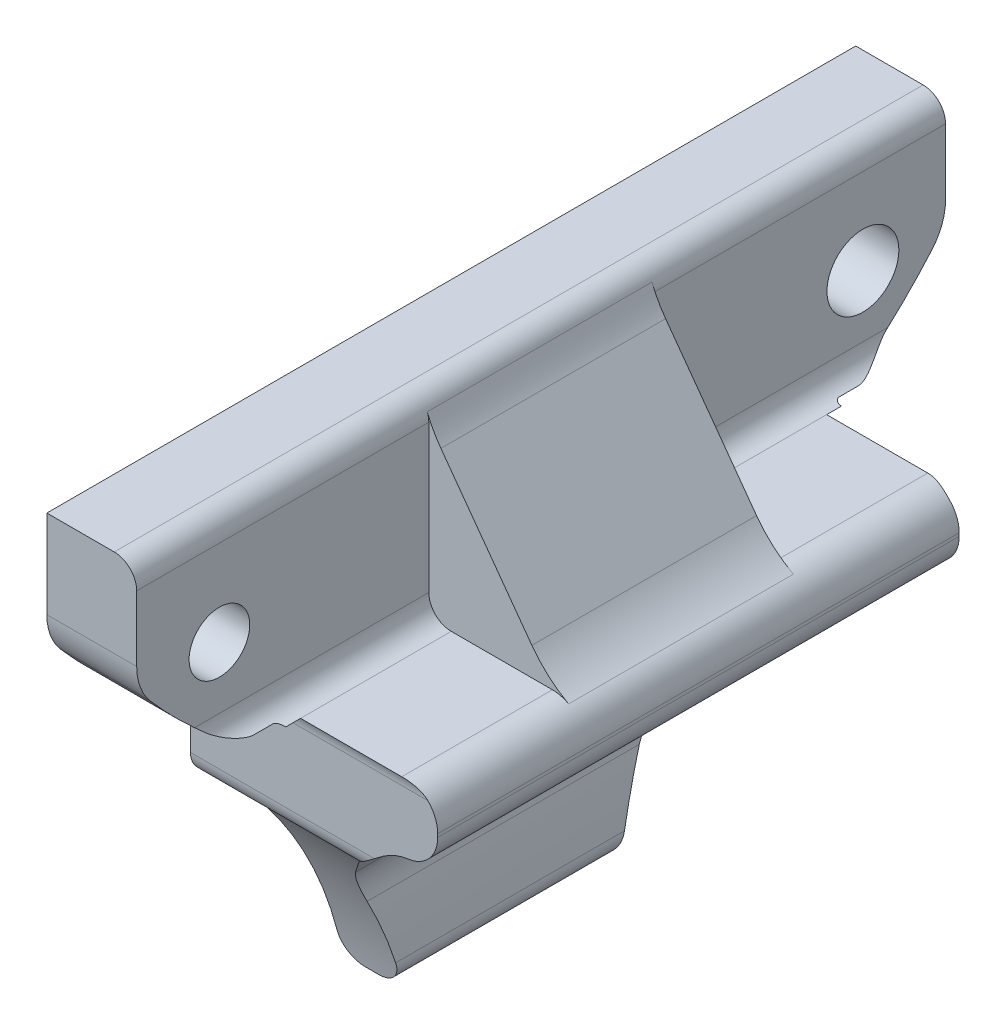
SolidWorks part; units mm, degrees
ref_plane "Front Plane" through (0, 0, 0) normal (0, 0, 1) x (1, 0, 0)
ref_plane "Top Plane" through (0, 0, 0) normal (0, 1, 0) x (1, 0, 0)
ref_plane "Right Plane" through (0, 0, 0) normal (1, 0, 0) x (0, 0, -1)
other "Configuration Table"
sketch "草图2" plane through (-34.0588, 0, 0) normal (1, 0, 0) x (0, 0, -1)
  line L0 (17.5003, 153.1924) -> (17.5003, 126.3596) construction
  line L1 (-17.4997, 126.3596) -> (-17.4997, 153.1924) construction
  line L2 (13.4167, 122.276) -> (8.6003, 122.276) construction
  line L3 (-4.8294, 122.276) -> (8.5706, 122.276) construction
  line L4 (-4.8997, 122.276) -> (-13.4161, 122.276) construction
  line L5 (17.5003, 130.276) -> (17.5003, 126.3596)
  line L6 (-17.4997, 126.3596) -> (-17.4997, 130.276)
  line L7 (13.4167, 122.276) -> (8.5706, 122.276)
  line L8 (-4.8294, 122.276) -> (8.5706, 122.276)
  line L9 (-4.8294, 122.276) -> (-13.4161, 122.276)
  line L10 (-17.4997, 130.276) -> (17.5003, 130.276)
  arc A0 (-17.4997, 126.3596) -> (-17.0119, 125.0507) centre (-15.4997, 126.3596) ccw construction
  arc A1 (17.0125, 125.0507) -> (17.5003, 126.3596) centre (15.5003, 126.3596) ccw construction
  arc A2 (14.7256, 122.7638) -> (17.0125, 125.0507) centre (0.0003, 139.776) ccw construction
  arc A3 (13.4167, 122.276) -> (14.7256, 122.7638) centre (13.4167, 124.276) ccw construction
  arc A4 (-17.0119, 125.0507) -> (-14.725, 122.7638) centre (0.0003, 139.776) ccw construction
  arc A5 (-14.725, 122.7638) -> (-13.4161, 122.276) centre (-13.4161, 124.276) ccw construction
  arc A6 (-17.4997, 126.3596) -> (-17.0119, 125.0507) centre (-15.4997, 126.3596) ccw
  arc A7 (17.0125, 125.0507) -> (17.5003, 126.3596) centre (15.5003, 126.3596) ccw
  arc A8 (14.7256, 122.7638) -> (17.0125, 125.0507) centre (0.0003, 139.776) ccw
  arc A9 (13.4167, 122.276) -> (14.7256, 122.7638) centre (13.4167, 124.276) ccw
  arc A10 (-17.0119, 125.0507) -> (-14.725, 122.7638) centre (0.0003, 139.776) ccw
  arc A11 (-14.725, 122.7638) -> (-13.4161, 122.276) centre (-13.4161, 124.276) ccw
  dimension "D1" = 8
extrude "凸台-拉伸1" add sketch "草图2" along normal blind 4
sketch "草图3" plane through (-30.0588, 0, 0) normal (1, 0, 0) x (0, 0, -1)
  line L0 (-13.4161, 122.276) -> (13.4167, 122.276) construction
  line L1 (-11.604, 122.276) -> (11.604, 122.276)
  line L2 (-11.604, 122.276) -> (-11.604, 106.7151)
  line L3 (-11.604, 106.7151) -> (11.604, 106.7151)
  line L4 (11.604, 122.276) -> (11.604, 106.7151)
  line L5 (0, 122.276) -> (0, 113.7703) construction
  point P6 (0, 122.276)
extrude "凸台-拉伸2" add sketch "草图3" against normal up to surface (67.5257 mm away)
sketch "草图7" plane through (0, 0, 11.604) normal (0, 0, 1) x (1, 0, 0)
  line L1 (-30.0588, 106.7151) -> (-23.0588, 106.7151)
  line L2 (-30.0588, 106.7151) -> (-30.0588, 121.7151)
  line L3 (-30.0588, 121.7151) -> (-23.0588, 121.7151)
  line L4 (-23.0588, 106.7151) -> (-23.0588, 121.7151)
  dimension "D1" = 7
  dimension "D2" = 15
extrude "凸台-拉伸3" add sketch "草图7" against normal up to surface (23.208 mm away) up to face at (-32.0588, 114.4955, -11.604)
sketch "草图11" plane through (0, 0, 11.604) normal (0, 0, 1) x (1, 0, 0)
  line L5 (-17.2607, 105.5707) -> (-17.8223, 118.1579)
  line L6 (-31.3247, 103.9771) -> (-17.2607, 105.5707)
  arc A11 (-25.4882, 118.1345) -> (-31.2955, 112.3272) centre (-10.0588, 96.8978) ccw
  arc A12 (-23.6542, 118.5853) -> (-25.4882, 118.1345) centre (-24.0187, 116.112) ccw
  arc A13 (-31.2955, 112.3272) -> (-31.7462, 110.4933) centre (-29.273, 110.8577) ccw
  arc A15 (-23.6542, 118.5853) -> (-17.8223, 118.1579) centre (-17.8223, 158.1579) ccw
  arc A17 (-31.3814, 106.8978) -> (-31.7462, 110.4933) centre (-71.3188, 104.6614) ccw
  arc A19 (-31.3247, 103.9771) -> (-31.3814, 106.8978) centre (-71.3188, 104.6614) ccw
extrude "切除-拉伸6" cut sketch "草图11" against normal blind 25
sketch "草图5" plane through (-30.0588, 0, 0) normal (1, 0, 0) x (0, 0, -1)
  arc A0 (-15.5686, 125.4571) -> (-13.0686, 125.4571) centre (-14.3186, 125.4571) ccw construction
  circle A1 centre (-14.3186, 125.4571) radius 1.25 construction
  arc A2 (15.5692, 125.4571) -> (13.0692, 125.4571) centre (14.3192, 125.4571) ccw construction
  circle A3 centre (14.3192, 125.4571) radius 1.25 construction
  circle A4 centre (-14.3186, 125.4571) radius 1.35
  circle A5 centre (14.3192, 125.4571) radius 1.6
  dimension "D1" = 2.7
  dimension "D2" = 3.2
extrude "切除-拉伸2" cut sketch "草图5" against normal blind 41
sketch "草图9" plane through (-30.0588, 0, 0) normal (1, 0, 0) x (0, 0, -1)
  circle A0 centre (-14.3186, 125.4571) radius 2.85
  circle A1 centre (14.3192, 125.4571) radius 2.85
  dimension "D1" = 5.7
  dimension "D2" = 5.7
extrude "切除-拉伸5" [suppressed] cut sketch "草图9" against normal blind 2
fillet "圆角7" [suppressed] radius 0.2
sketch "草图13" plane through (-34.0588, 0, 0) normal (-1, 0, 0) x (0, 0, 1)
  line L0 (-0.0003, 130.276) -> (0, 109.4709) construction
  line L1 (-17.5003, 130.276) -> (17.4997, 130.276) construction
  circle A0 centre (-15, 109.4709) radius 7.5
  circle A1 centre (15, 109.4714) radius 7.5
  dimension "D1" = 15
  dimension "D2" = 15
extrude "切除-拉伸7" [suppressed] cut sketch "草图13" against normal blind 14
fillet "圆角1" radius 1 2 edges at (-32.0588, 122.276, -11.604) (-32.0588, 122.276, 11.604)
sketch "草图16" plane through (-30.0588, 0, 0) normal (1, 0, 0) x (0, 0, -1)
  line L0 (22.0003, 103.276) -> (-14.3831, 103.276) construction
  line L1 (17.5003, 130.276) -> (-17.4997, 130.276) construction
  line L2 (0.0003, 130.276) -> (0.0003, 83.1608) construction
  circle A0 centre (22.0003, 103.276) radius 17.5
  circle A1 centre (-21.9997, 103.276) radius 17.5
  dimension "D2" = 35
  dimension "D1" = 27
  dimension "D3" = 22
extrude "切除-拉伸9" cut sketch "草图16" against normal through all both and the other way through all
sketch "草图17" plane through (-30.0588, 0, 0) normal (1, 0, 0) x (0, 0, -1)
  line L9 (-13.4161, 122.276) -> (-12.604, 122.276) construction
  line L14 (-17.4997, 130.276) -> (-17.4997, 126.3596) construction
  line L15 (-13.4161, 122.276) -> (-12.604, 122.276)
  line L16 (-17.4997, 130.276) -> (-17.4997, 126.3596)
  line L19 (-17.9997, 130.276) -> (-17.4997, 130.276)
  line L22 (-17.9997, 129.776) -> (-17.9997, 129.776)
  line L23 (-17.9997, 129.776) -> (-17.9997, 126.3596)
  line L24 (-13.4161, 121.776) -> (-12.604, 121.776)
  line L25 (-11.7055, 121.7151) -> (-12.3648, 121.7151)
  line L26 (-17.9997, 130.276) -> (-17.9997, 129.776)
  arc A4 (-11.7055, 121.7151) -> (-12.604, 122.276) centre (-12.604, 121.276) ccw construction
  arc A5 (-14.725, 122.7638) -> (-13.4161, 122.276) centre (-13.4161, 124.276) ccw construction
  arc A6 (-17.0119, 125.0507) -> (-14.725, 122.7638) centre (0.0003, 139.776) ccw construction
  arc A7 (-17.4997, 126.3596) -> (-17.0119, 125.0507) centre (-15.4997, 126.3596) ccw construction
  arc A9 (-11.7055, 121.7151) -> (-12.604, 122.276) centre (-12.604, 121.276) ccw
  arc A10 (-14.725, 122.7638) -> (-13.4161, 122.276) centre (-13.4161, 124.276) ccw
  arc A21 (-17.0119, 125.0507) -> (-14.725, 122.7638) centre (0.0003, 139.776) ccw
  arc A30 (-17.4997, 126.3596) -> (-17.0119, 125.0507) centre (-15.4997, 126.3596) ccw
  arc A36 (-17.9997, 126.3596) -> (-17.3899, 124.7235) centre (-15.4997, 126.3596) ccw
  arc A37 (-17.3899, 124.7235) -> (-15.0522, 122.3858) centre (0.0003, 139.776) ccw
  arc A38 (-15.0522, 122.3858) -> (-13.4161, 121.776) centre (-13.4161, 124.276) ccw
  arc A39 (-12.3648, 121.7151) -> (-12.604, 121.776) centre (-12.604, 121.276) ccw
  arc A41 (-12.1548, 121.4955) -> (-12.604, 121.776) centre (-12.604, 121.276) ccw construction
  arc A42 (-12.104, 121.276) -> (-12.1548, 121.4955) centre (-12.604, 121.276) ccw construction
  arc A43 (-11.604, 121.276) -> (-11.7055, 121.7151) centre (-12.604, 121.276) ccw construction
  dimension "D1" = 0.5
extrude "凸台-拉伸5" add sketch "草图17" against normal up to surface (4 mm away) up to face at (-34.0588, 127.0571, -14.3192)
ref_plane "基准面1" through (0, 0, 0) normal (0, 0, 1) x (1, 0, 0)
mirror "镜向1" about plane through (0, 0, 0) normal (0, 0, 1) of "凸台-拉伸5"
fillet "圆角8" radius 1 2 edges at (-30.2844, 117.3532, -11.604) (-30.2841, 117.3536, 11.604)
fillet "圆角10" radius 1 1 edges at (-30.0588, 130.276, 0)
fillet "圆角12" radius 1 2 edges at (-31.3716, 106.7151, -0.0003) (-34.0588, 106.7151, -0.0003)
fillet "圆角13" radius 1.5 2 edges at (-23.0588, 121.7151, 0) (-23.0588, 118.5021, 0)
ref_plane "基准面2" through (0, 0, 0) normal (0, 0, 1) x (1, 0, 0)
sketch "草图19" plane through (0, 0, 0) normal (0, 0, 1) x (1, 0, 0)
  line L0 (-30.0588, 129.276) -> (-24.5588, 121.7151)
rib "筋1" sketch "草图19" sketch "草图19" thickness 10 extrusion direction parallel to sketch draft on no parameters "D1"=10
fillet "圆角14" radius 1 2 edges at (-30.0588, 121.7151, -8.3528) (-30.0588, 121.7151, 8.3528)
fillet "圆角15" radius 5 2 edges at (-30.0588, 129.276, 0) (-24.5588, 121.7151, 0)
